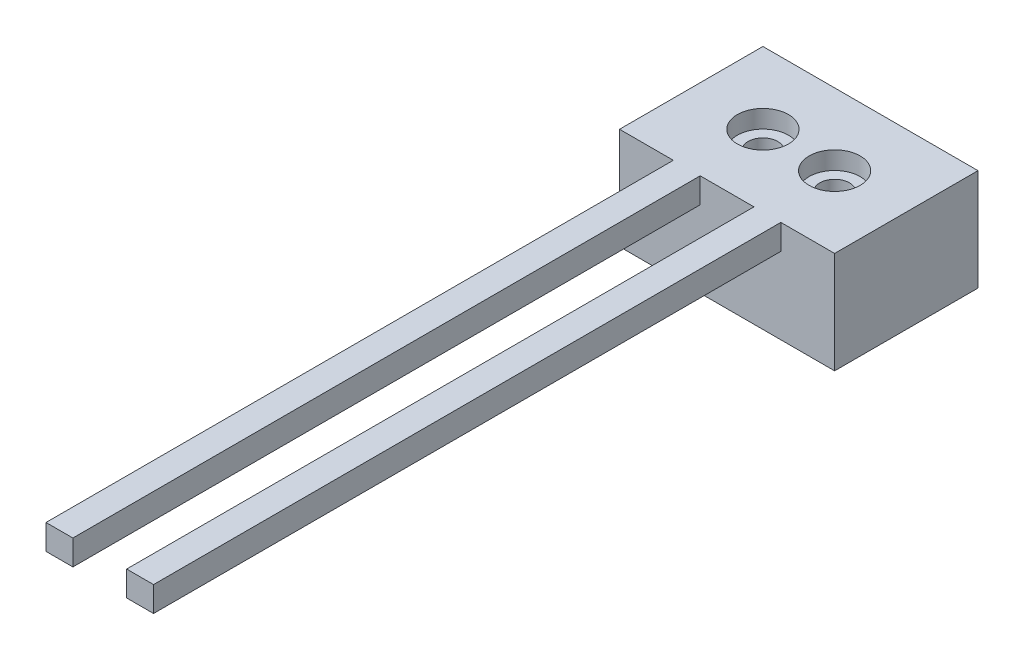
SolidWorks part; units mm, degrees
ref_plane "Front Plane" through (0, 0, 0) normal (0, 0, 1) x (1, 0, 0)
ref_plane "Top Plane" through (0, 0, 0) normal (0, 1, 0) x (1, 0, 0)
ref_plane "Right Plane" through (0, 0, 0) normal (1, 0, 0) x (0, 0, -1)
sketch "Sketch1" plane through (0, 0, 0) normal (0, -1, 0) x (1, 0, 0)
  line L0 (0, -8) -> (8, -8) construction
  line L1 (0, 0) -> (24, 0)
  line L2 (0, 0) -> (0, -16)
  line L3 (0, -16) -> (24, -16)
  line L4 (24, 0) -> (24, -16)
  line L5 (8, -8) -> (16, -8) construction
  line L6 (16, -8) -> (24, -8) construction
  circle A0 centre (8, -8) radius 1.65
  circle A1 centre (16, -8) radius 1.65
  dimension "D3" = 3.3
  dimension "D1" = 16
  dimension "D2" = 24
extrude "Boss-Extrude1" add sketch "Sketch1" along normal blind 11.35
sketch "Sketch2" plane through (0, 0, 0) normal (0, 0, 1) x (1, 0, 0)
  line L0 (24, 0) -> (0, 0) construction
  line L1 (6, 0) -> (9, 0)
  line L2 (6, 0) -> (6, -2.8)
  line L3 (6, -2.8) -> (9, -2.8)
  line L4 (9, 0) -> (9, -2.8)
  line L5 (0, 0) -> (6, 0) construction
  line L6 (15, 0) -> (18, 0)
  line L7 (15, 0) -> (15, -2.8)
  line L8 (15, -2.8) -> (18, -2.8)
  line L9 (18, 0) -> (18, -2.8)
  line L10 (9, 0) -> (15, 0) construction
  line L11 (18, 0) -> (24, 0) construction
  dimension "D1" = 2.8
  dimension "D2" = 3
  dimension "D3" = 3
extrude "Boss-Extrude2" add sketch "Sketch2" along normal blind 70
sketch "Sketch3" plane through (0, 0, 0) normal (0, 1, 0) x (1, 0, 0)
  circle A0 centre (8, 8) radius 2.85
  circle A1 centre (16, 8) radius 2.85
  dimension "D1" = 5.7
extrude "Cut-Extrude1" cut sketch "Sketch3" against normal blind 2
